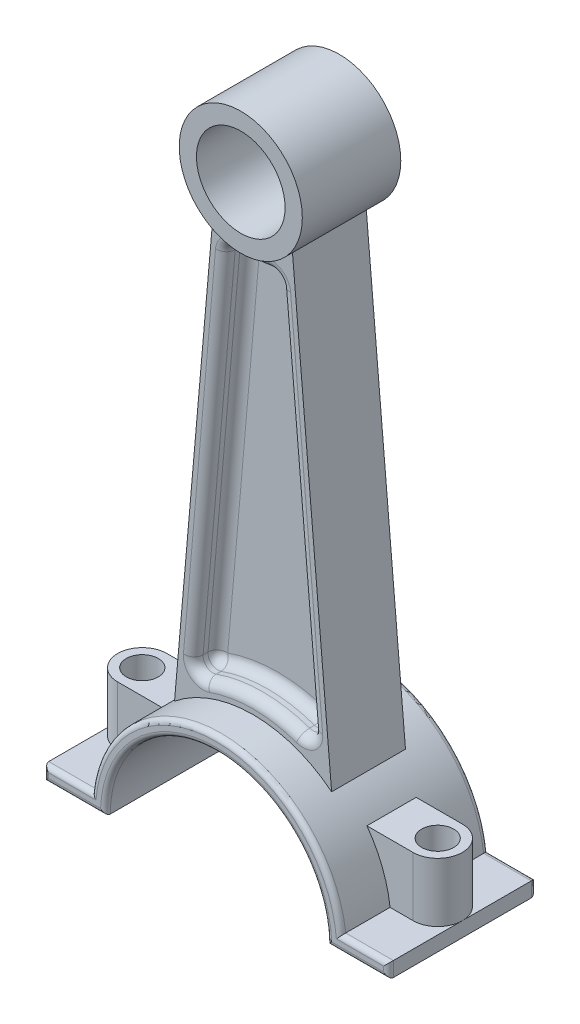
SolidWorks part; units mm, degrees
ref_plane "Front Plane" through (0, 0, 0) normal (0, 0, 1) x (1, 0, 0)
ref_plane "Top Plane" through (0, 0, 0) normal (0, 1, 0) x (1, 0, 0)
ref_plane "Right Plane" through (0, 0, 0) normal (1, 0, 0) x (0, 0, -1)
sketch "Sketch1" plane through (0, 0, 0) normal (0, 0, 1) x (1, 0, 0)
  line L0 (0, 0) -> (0, -97.9) construction
  line L1 (-35, -120.4) -> (-22.5, -120.4)
  line L2 (22.5, -120.4) -> (35, -120.4)
  line L3 (0, -97.9) -> (0, -120.4) construction
  line L4 (25.3229, -117.4) -> (35, -117.4)
  line L5 (-35, -117.4) -> (-25.3229, -117.4)
  line L6 (-35, -117.4) -> (-35, -120.4)
  line L7 (35, -117.4) -> (35, -120.4)
  line L8 (-8, -9.6047) -> (-15.9529, -100.5064)
  line L9 (8, -9.6047) -> (15.9529, -100.5064)
  circle A0 centre (0, 0) radius 9
  circle A1 centre (0, 0) radius 12.5
  arc A2 (22.5, -120.4) -> (-22.5, -120.4) centre (0, -120.4) ccw
  arc A3 (25.3229, -117.4) -> (-25.3229, -117.4) centre (0, -120.4) ccw
  point P10 (0, -120.4)
  point P12 (0, -120.4)
  dimension "D1" = 25
  dimension "D2" = 18
  dimension "D4" = 45
  dimension "D3" = 120.4
  dimension "D5" = 70
  dimension "D7" = 5
  dimension "D8" = 8
  dimension "D6" = 3
extrude "Boss-Extrude1" add sketch "Sketch1" along normal mid plane 20 contours A1 A0 region at (-5.1533, 10.9991, 0)
extrude "Boss-Extrude2" add sketch "Sketch1<3>" along normal mid plane 30 separate body contours L4 A3 L5 L6 L1 A2 L2 L7 region at (-34.255, -118.9, 0)
sketch "Sketch1<3>" plane through (0, 0, 0) normal (0, 0, 1) x (1, 0, 0) same geometry as "Sketch1"
extrude "Boss-Extrude3" add sketch "Sketch1<4>" along normal mid plane 15 contours A3 L9 A1 L8 region at (0, -58.5545, 0)
sketch "Sketch1<4>" plane through (0, 0, 0) normal (0, 0, 1) x (1, 0, 0) same geometry as "Sketch1"
sketch "Sketch2" plane through (0, 0, 0) normal (0, 0, 1) x (1, 0, 0)
  line L8 (12.4385, -94.7576) -> (5.4187, -14.522)
  line L9 (-5.4187, -14.522) -> (-12.4385, -94.7576)
  line L10 (12.4385, -94.7576) -> (5.4187, -14.522)
  line L11 (-5.4187, -14.522) -> (-12.4385, -94.7576)
  arc A8 (12.4385, -94.7576) -> (-12.4385, -94.7576) centre (0, -120.4) ccw
  arc A9 (-5.4187, -14.522) -> (5.4187, -14.522) centre (0, 0) ccw
  arc A10 (12.4385, -94.7576) -> (-12.4385, -94.7576) centre (0, -120.4) ccw
  arc A11 (-5.4187, -14.522) -> (5.4187, -14.522) centre (0, 0) ccw
  dimension "D2" = 3
extrude "Cut-Extrude1" cut sketch "Sketch2" against normal blind 5 from offset 7.5 contours A10 L11 A11 L10
mirror "Mirror1" about plane through (0, 0, 0) normal (0, 0, 1) of "Cut-Extrude1"
sketch "Sketch3" plane through (0, -117.4, 0) normal (0, 1, 0) x (1, 0, 0)
  line L0 (35, -15) -> (35, 15) construction
  line L1 (18, 5) -> (30, 5)
  line L2 (18, 5) -> (18, -5)
  line L3 (18, -5) -> (30, -5)
  line L4 (30, 5) -> (30, -5)
  line L5 (18, 5) -> (30, -5) construction
  line L6 (18, -5) -> (30, 5) construction
  circle A0 centre (30, 0) radius 5
  circle A1 centre (30, 0) radius 3.25
  point P0 (24, 0)
  line M7 (25.3229, 15) -> (25.3229, -15)
  dimension "D1" = 10
  dimension "D4" = 6.5
  dimension "D2" = 12
  dimension "D3" = 10
extrude "Boss-Extrude5" add sketch "Sketch3" against normal up to body from offset 12 separate body contours A0 L1 L2 L3 M7 | A0 L3 M7 | A0 L1 M7 | A0 region at (21.6241, -117.4, 0) region at (26.4044, -117.4, -4.1253) region at (26.4044, -117.4, 4.1253)
extrude "Cut-Extrude2" cut sketch "Sketch3<6>" against normal through all from surface separate body contours L4 A1 | L4 A1 region at (31.3793, -117.4, 0) region at (28.6207, -117.4, 0) starting at face at (26.5608, -105.4, 0)
sketch "Sketch3<6>" plane through (0, -117.4, 0) normal (0, 1, 0) x (1, 0, 0) same geometry as "Sketch3"
mirror "Mirror2" about plane through (0, 0, 0) normal (1, 0, 0) of "Cut-Extrude2", "Boss-Extrude5"
fillet "Fillet1" radius 2 20 edges at (8.9286, -54.6398, 7.5) (0, -15.5, -7.5) (8.9286, -54.6398, -7.5) (0, -15.5, 7.5) (0, -91.9, 7.5) (0, -15.5, -2.5) (-8.9286, -54.6398, -2.5) (0, -91.9, -2.5) (8.9286, -54.6398, -2.5) (-8.9286, -54.6398, -7.5) (-5.4187, -14.522, -5) (5.4187, -14.522, -5) (-12.4385, -94.7576, -5) (12.4385, -94.7576, -5) (0, -91.9, -7.5) (-8.9286, -54.6398, 7.5) (5.4187, -14.522, 5) (-5.4187, -14.522, 5) (12.4385, -94.7576, 5) (-12.4385, -94.7576, 5)
fillet "Fillet2" radius 2 8 edges at (11.3832, -93.2222, 2.5) (8.8906, -54.2052, 2.5) (4.8279, -15.5099, 2.5) (0, -15.5, 2.5) (-4.8279, -15.5099, 2.5) (-8.8906, -54.2052, 2.5) (-11.3832, -93.2222, 2.5) (0, -91.9, 2.5)
fillet "Fillet3" radius 1 16 edges at (35, -118.9, 15) (28.75, -120.4, 15) (0, -97.9, 15) (-28.75, -120.4, 15) (-35, -118.9, 15) (-30.1615, -117.4, 15) (0, -94.9, 15) (30.1615, -117.4, 15) (0, -94.9, -15) (-30.1615, -117.4, -15) (-35, -118.9, -15) (-28.75, -120.4, -15) (0, -97.9, -15) (28.75, -120.4, -15) (35, -118.9, -15) (30.1615, -117.4, -15)
